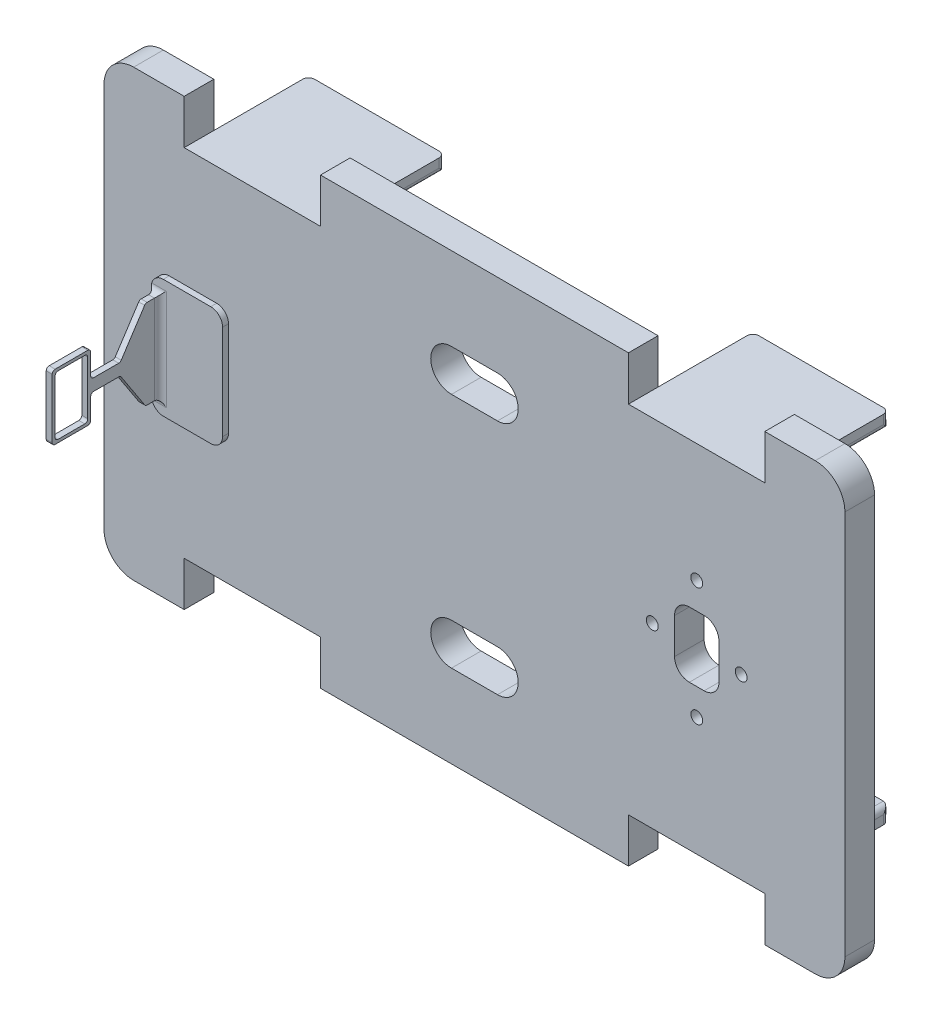
SolidWorks part; units mm, degrees
material "ABS PC"
ref_plane "Front Plane" through (0, 0, 0) normal (0, 0, 1) x (1, 0, 0)
ref_plane "Top Plane" through (0, 0, 0) normal (0, 1, 0) x (1, 0, 0)
ref_plane "Right Plane" through (0, 0, 0) normal (1, 0, 0) x (0, 0, -1)
sketch "Sketch1" plane through (0, 0, 0) normal (0, 0, 1) x (1, 0, 0)
  line L1 (-125, 75) -> (125, 75)
  line L2 (-125, 75) -> (-125, -75)
  line L3 (-125, -75) -> (125, -75)
  line L4 (125, 75) -> (125, -75)
  line L5 (-125, 75) -> (125, -75) construction
  line L6 (-125, -75) -> (125, 75) construction
  point P0 (0, 0)
  dimension "D1" = 250
  dimension "D2" = 150
extrude "Boss-Extrude1" add sketch "Sketch1" along normal mid plane 10
sketch "Sketch2" plane through (0, 0, 5) normal (0, 0, 1) x (1, 0, 0)
  line L0 (125, 75) -> (-125, 75) construction
  line L1 (-97.954, 90) -> (-51.954, 90)
  line L2 (-97.954, 90) -> (-97.954, 60)
  line L3 (-97.954, 60) -> (-51.954, 60)
  line L4 (-51.954, 90) -> (-51.954, 60)
  line L5 (-97.954, 90) -> (-51.954, 60) construction
  line L6 (-97.954, 60) -> (-51.954, 90) construction
  line L7 (0, -55) -> (0, 55) construction
  line L8 (97.954, 60) -> (51.954, 90) construction
  line L9 (97.954, 90) -> (51.954, 60) construction
  line L10 (51.954, 90) -> (51.954, 60)
  line L11 (97.954, 60) -> (51.954, 60)
  line L12 (97.954, 90) -> (97.954, 60)
  line L13 (97.954, 90) -> (51.954, 90)
  line L14 (55, 0) -> (-55, 0) construction
  line L15 (97.954, -90) -> (51.954, -60) construction
  line L16 (97.954, -60) -> (51.954, -90) construction
  line L17 (-97.954, -60) -> (-51.954, -90) construction
  line L18 (-97.954, -90) -> (-51.954, -60) construction
  line L19 (97.954, -90) -> (51.954, -90)
  line L20 (97.954, -90) -> (97.954, -60)
  line L21 (97.954, -60) -> (51.954, -60)
  line L22 (51.954, -90) -> (51.954, -60)
  line L23 (-51.954, -90) -> (-51.954, -60)
  line L24 (-97.954, -60) -> (-51.954, -60)
  line L25 (-97.954, -90) -> (-97.954, -60)
  line L26 (-97.954, -90) -> (-51.954, -90)
  point P0 (-74.954, 75)
  point P14 (74.954, 75)
  point P25 (74.954, -75)
  point P26 (-74.954, -75)
  dimension "D1" = 46
  dimension "D2" = 50.046
  dimension "D3" = 30
extrude "Cut-Extrude1" cut sketch "Sketch2" against normal through all
fillet "Fillet1" radius 10 1 edges at (125, -75, 0)
fillet "Fillet4" radius 10 3 edges at (125, 75, 0) (-125, 75, 0) (-125, -75, 0)
sketch "Sketch3" plane through (0, 0, 5) normal (0, 0, 1) x (1, 0, 0)
  line L0 (-7.7575, -40) -> (7.7575, -40) construction
  line L1 (-7.7575, -33) -> (7.7575, -33)
  line L2 (-7.7575, -47) -> (7.7575, -47)
  line L3 (55, 0) -> (-55, 0) construction
  line L4 (-7.7575, 40) -> (7.7575, 40) construction
  line L5 (-7.7575, 33) -> (7.7575, 33)
  line L6 (-7.7575, 47) -> (7.7575, 47)
  arc A0 (-7.7575, -33) -> (-7.7575, -47) centre (-7.7575, -40) ccw
  arc A1 (7.7575, -47) -> (7.7575, -33) centre (7.7575, -40) ccw
  arc A2 (-7.7575, 33) -> (-7.7575, 47) centre (-7.7575, 40) cw
  arc A3 (7.7575, 47) -> (7.7575, 33) centre (7.7575, 40) cw
  point P2 (0, -40)
  point P13 (0, 40)
  dimension "D3" = 7
  dimension "D1" = 15.5149
  dimension "D2" = 40
sketch "Sketch4" plane through (0, 0, 5) normal (0, 0, 1) x (1, 0, 0)
  line L1 (77.5, 11) -> (72.5, 11)
  line L2 (82.5, 6) -> (82.5, -6)
  line L3 (77.5, -11) -> (72.5, -11)
  line L4 (67.5, 6) -> (67.5, -6)
  line L5 (82.5, 11) -> (67.5, -11) construction
  line L6 (82.5, -11) -> (67.5, 11) construction
  arc A0 (72.5, -11) -> (67.5, -6) centre (72.5, -6) cw
  arc A1 (72.5, 11) -> (67.5, 6) centre (72.5, 6) ccw
  arc A2 (82.5, -6) -> (77.5, -11) centre (77.5, -6) cw
  arc A3 (77.5, 11) -> (82.5, 6) centre (77.5, 6) cw
  point P0 (75, 0)
  dimension "D4" = 5
  dimension "D5" = 5
  dimension "D6" = 5
  dimension "D7" = 5
  dimension "D1" = 15
  dimension "D2" = 22
  dimension "D3" = 75
sketch "Sketch5" plane through (0, 0, 5) normal (0, 0, 1) x (1, 0, 0)
  circle A0 centre (90, 0) radius 2
  circle A1 centre (75, 20) radius 2
  circle A2 centre (60, 0) radius 2
  circle A3 centre (75, -20) radius 2
  dimension "D1" = 4
  dimension "D6" = 4
  dimension "D3" = 15
  dimension "D4" = 4
  dimension "D5" = 4
  dimension "D2" = 15
  dimension "D7" = 20
  dimension "D8" = 20
extrude "Cut-Extrude2" cut sketch "Sketch5" against normal through all
extrude "Cut-Extrude3" cut sketch "Sketch4" against normal through all
extrude "Cut-Extrude4" cut sketch "Sketch3" against normal through all
sketch "Sketch9" plane through (0, 0, 5) normal (0, 0, 1) x (1, 0, 0)
  line L1 (-103, 20) -> (-87, 20)
  line L2 (-107, 16) -> (-107, -16)
  line L3 (-103, -20) -> (-87, -20)
  line L4 (-83, 16) -> (-83, -16)
  line L5 (-107, 20) -> (-83, -20) construction
  line L6 (-107, -20) -> (-83, 20) construction
  arc A0 (-103, 20) -> (-107, 16) centre (-103, 16) ccw
  arc A1 (-107, -16) -> (-103, -20) centre (-103, -16) ccw
  arc A2 (-87, -20) -> (-83, -16) centre (-87, -16) ccw
  arc A3 (-87, 20) -> (-83, 16) centre (-87, 16) cw
  point P0 (-95, 0)
  dimension "D4" = 4
  dimension "D5" = 4
  dimension "D6" = 4
  dimension "D7" = 4
  dimension "D1" = 95
  dimension "D2" = 24
  dimension "D3" = 40
extrude "Boss-Extrude2" add sketch "Sketch9" along normal blind 2
sketch "Sketch11" plane through (0, 0, 7) normal (0, 0, 1) x (1, 0, 0)
  line L1 (-106, 15) -> (-104, 15)
  line L2 (-106, 15) -> (-106, -15)
  line L3 (-106, -15) -> (-104, -15)
  line L4 (-104, 15) -> (-104, -15)
  line L5 (-106, 15) -> (-104, -15) construction
  line L6 (-106, -15) -> (-104, 15) construction
  point P0 (-105, 0)
  dimension "D1" = 30
  dimension "D2" = 2
  dimension "D3" = 105
extrude "Boss-Extrude3" add sketch "Sketch11" along normal blind 40
fillet "Fillet5" radius 2 1 edges at (-104, 0, 7)
fillet "Fillet6" radius 2 1 edges at (-104, -15, 7)
fillet "Fillet7" radius 2 1 edges at (-104, 15, 7)
fillet "Fillet8" radius 2 1 edges at (-106, 0, 7)
sketch "Sketch12" plane through (-106, 0, 0) normal (-1, 0, 0) x (0, 0, 1)
  line L0 (47, 15) -> (47, -15) construction
  line L1 (30.5, 11) -> (43.5, 11)
  line L2 (30.5, 11) -> (30.5, -11)
  line L3 (30.5, -11) -> (43.5, -11)
  line L4 (43.5, 11) -> (43.5, -11)
  line L5 (30.5, 11) -> (43.5, -11) construction
  line L6 (30.5, -11) -> (43.5, 11) construction
  line L7 (30.5, 2) -> (20.5, 2)
  line L8 (20.5, 2) -> (12, 15)
  line L9 (47, 15) -> (9, 15) construction
  line L10 (37, 0) -> (8.7321, 0) construction
  line L11 (8.7321, 15.018) -> (8.7321, -15.018) construction
  line L12 (30.5, -2) -> (20.5, -2)
  line L13 (20.5, -2) -> (12, -15)
  line L14 (31.5, 10) -> (31.5, -10)
  line L15 (31.5, -10) -> (42.5, -10)
  line L16 (42.5, 10) -> (42.5, -10)
  line L17 (31.5, 10) -> (42.5, 10)
  point P0 (37, 0)
  point P7 (47, 0)
  point P17 (30.5, 0)
  line M11 (9, -15) -> (47, -15)
  line M12 (47, -15) -> (47, 15)
  line M13 (47, 15) -> (9, 15)
  dimension "D1" = 10
  dimension "D2" = 22
  dimension "D3" = 13
  dimension "D4" = 10
  dimension "D5" = 35
  dimension "D6" = 2
  dimension "D7" = 1
extrude "Cut-Extrude6" cut sketch "Sketch12" against normal through all contours L17 L14 L15 L16 | L12 L13 L8 L7 L2 L1 L4 L3 M11 M12 M13 region at (-106, 6.5, 30.039) region at (-106, 0, 37)
fillet "Fillet9" radius 1 10 edges at (-105, -11, 43.5) (-105, -15, 12) (-105, -2, 20.5) (-105, -2, 30.5) (-105, -11, 30.5) (-105, 2, 30.5) (-105, 11, 43.5) (-105, 11, 30.5) (-105, 2, 20.5) (-105, 15, 12)
fillet "Fillet10" radius 1 4 edges at (-105, -10, 31.5) (-105, 10, 42.5) (-105, 10, 31.5) (-105, -10, 42.5)
sketch "Sketch13" plane through (0, 0, -5) normal (0, 0, -1) x (-1, 0, 0)
  line L0 (51.954, 60) -> (51.954, 55)
  line L1 (51.954, 55) -> (97.954, 55)
  line L2 (97.954, 55) -> (97.954, 60)
  line L3 (55, 0) -> (-55, 0) construction
  line L4 (97.954, -60) -> (51.954, -60)
  line L5 (97.954, -55) -> (97.954, -60)
  line L6 (51.954, -55) -> (97.954, -55)
  line L7 (51.954, -60) -> (51.954, -55)
  line L8 (0, 55) -> (0, -55) construction
  line L9 (-51.954, -60) -> (-51.954, -55)
  line L10 (-51.954, -55) -> (-97.954, -55)
  line L11 (-97.954, -55) -> (-97.954, -60)
  line L12 (-97.954, -60) -> (-51.954, -60)
  line L13 (-97.954, 60) -> (-51.954, 60)
  line L14 (-97.954, 55) -> (-97.954, 60)
  line L15 (-51.954, 55) -> (-97.954, 55)
  line L16 (-51.954, 60) -> (-51.954, 55)
  line L23 (-97.954, 75) -> (-115, 75)
  line L24 (-125, 65) -> (-125, -65)
  line L25 (-115, -75) -> (-97.954, -75)
  line L26 (-97.954, -75) -> (-97.954, -60)
  line L27 (-97.954, -60) -> (-51.954, -60)
  line L28 (-51.954, -60) -> (-51.954, -75)
  line L29 (-51.954, -75) -> (51.954, -75)
  line L30 (51.954, -75) -> (51.954, -60)
  line L31 (51.954, -60) -> (97.954, -60)
  line L32 (97.954, -60) -> (97.954, -75)
  line L33 (97.954, -75) -> (115, -75)
  line L34 (125, -65) -> (125, 65)
  line L35 (115, 75) -> (97.954, 75)
  line L36 (97.954, 75) -> (97.954, 60)
  line L37 (97.954, 60) -> (51.954, 60)
  line L38 (51.954, 60) -> (51.954, 75)
  line L39 (51.954, 75) -> (-51.954, 75)
  line L40 (-51.954, 75) -> (-51.954, 60)
  line L41 (-51.954, 60) -> (-97.954, 60)
  line L42 (-97.954, 60) -> (-97.954, 75)
  line L57 (97.954, 60) -> (51.954, 60)
  arc A4 (-115, 75) -> (-125, 65) centre (-115, 65) ccw
  arc A5 (-125, -65) -> (-115, -75) centre (-115, -65) ccw
  arc A6 (115, -75) -> (125, -65) centre (115, -65) ccw
  arc A7 (125, 65) -> (115, 75) centre (115, 65) ccw
  dimension "D1" = 5
  dimension "D2" = 0
extrude "Boss-Extrude5" add sketch "Sketch13" along normal blind 32 contours L1 L2 L57 L0 | L9 L10 L11 L12 | L4 L7 L6 L5 | L14 L13 L16 L15
fillet "Fillet11" radius 2 16 edges at (-51.954, -55, -21) (97.954, -55, -21) (51.954, -55, -21) (-97.954, -55, -21) (-97.954, -57.5, -37) (-51.954, -57.5, -37) (97.954, -57.5, -37) (51.954, -57.5, -37) (51.954, 55, -21) (51.954, 57.5, -37) (97.954, 57.5, -37) (97.954, 55, -21) (-51.954, 55, -21) (-97.954, 55, -21) (-51.954, 57.5, -37) (-97.954, 57.5, -37)
sketch "Sketch14" plane through (-106, 0, 0) normal (-1, 0, 0) x (0, 0, 1)
  line L0 (42.2071, 9.7071) -> (31.7929, -9.7071) construction
  line L1 (31.7929, 9.7071) -> (42.2071, -9.7071) construction
  arc A0 (42.5, 9) -> (41.5, 10) centre (41.5, 9) ccw construction
  arc A1 (31.5, -9) -> (32.5, -10) centre (32.5, -9) ccw construction
  arc A2 (32.5, 10) -> (31.5, 9) centre (32.5, 9) ccw construction
  arc A3 (41.5, -10) -> (42.5, -9) centre (41.5, -9) ccw construction
ref_point "Point1"
